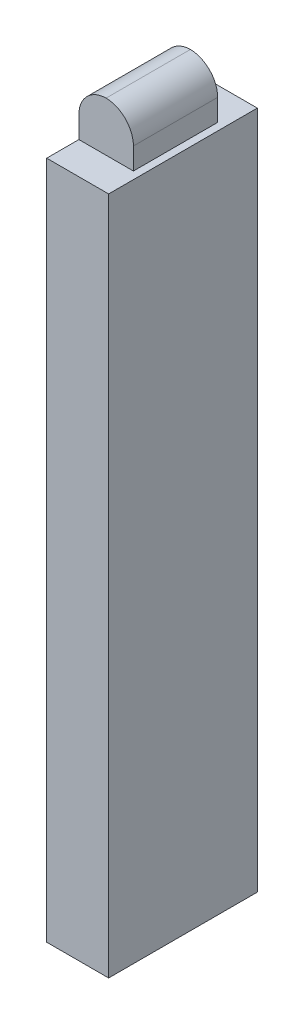
SolidWorks part; units mm, degrees
ref_plane "Front Plane" through (0, 0, 0) normal (1, 0, 0) x (0, 1, 0)
ref_plane "Top Plane" through (0, 0, 0) normal (0, 0, 1) x (0, 1, 0)
ref_plane "Right Plane" through (0, 0, 0) normal (0, 1, 0) x (-1, 0, 0)
sketch "Sketch1" plane through (0, 0, 0) normal (1, 0, 0) x (0, 1, 0)
  line L1 (-54.8, -12) -> (54.8, -12)
  line L2 (-54.8, -12) -> (-54.8, 12)
  line L3 (-54.8, 12) -> (54.8, 12)
  line L4 (54.8, -12) -> (54.8, 12)
  line L5 (-54.8, -12) -> (54.8, 12) construction
  line L6 (-54.8, 12) -> (54.8, -12) construction
  line L7 (44.8, 10) -> (-54.8, 10)
  line L8 (44.8, 10) -> (44.8, -10)
  line L9 (44.8, -10) -> (-54.8, -10)
  line L10 (-54.8, 10) -> (-54.8, -10)
  point P0 (0, 0)
  point P10 (0, 0)
  dimension "D1" = 24
  dimension "D2" = 109.6
  dimension "D3" = 2
  dimension "D4" = 2
  dimension "D5" = 10
extrude "Boss-Extrude1" add sketch "Sketch1" along normal blind 10 contours L3 L4 L1 L2
sketch "Sketch3" plane through (0, 54.8, 0) normal (0, 1, 0) x (-1, 0, 0)
  line L1 (-8.8, 6.8) -> (0, 6.8)
  line L2 (-8.8, 6.8) -> (-8.8, -6.8)
  line L3 (-8.8, -6.8) -> (0, -6.8)
  line L4 (0, 6.8) -> (0, -6.8)
  line L5 (0, -12) -> (0, 12) construction
  line L6 (-10, -12) -> (0, -12) construction
  line L7 (-10, 12) -> (0, 12) construction
  line L9 (-10, -12) -> (-10, 12) construction
  dimension "D1" = 5.2
  dimension "D2" = 5.2
  dimension "D3" = 1.2
  dimension "D4" = 13.6
extrude "Boss-Extrude2" add sketch "Sketch3" along normal blind 8
fillet "Fillet1" radius 4.5 2 edges at (0, 62.8, 0) (8.8, 62.8, 0)
